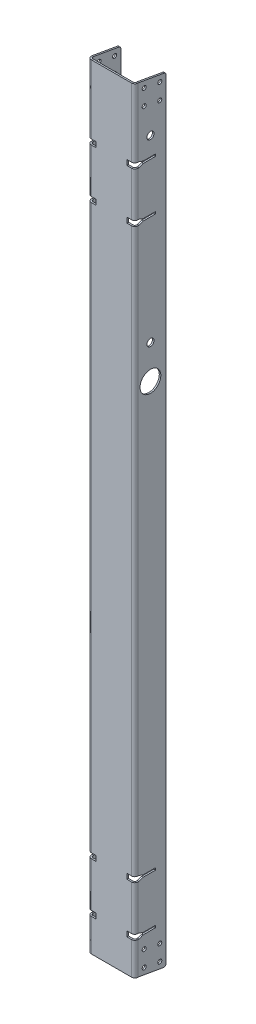
SolidWorks part; units mm, degrees
note: The reader was unsure of these and kept them because the rebuilt part matched: flange length of "Edge-Flange1", "Edge-Flange2".
ref_plane "Front Plane" through (0, 0, 0) normal (0, 0, 1) x (1, 0, 0)
ref_plane "Top Plane" through (0, 0, 0) normal (0, 1, 0) x (1, 0, 0)
ref_plane "Right Plane" through (0, 0, 0) normal (1, 0, 0) x (0, 0, -1)
sketch "Sketch1" plane through (0, 0, 0) normal (0, 0, 1) x (1, 0, 0)
  line L1 (28.575, 473.329) -> (-28.575, 473.329)
  line L2 (28.575, 473.329) -> (28.575, -473.329)
  line L3 (28.575, -473.329) -> (-28.575, -473.329)
  line L4 (-28.575, 473.329) -> (-28.575, -473.329)
  line L5 (28.575, 473.329) -> (-28.575, -473.329) construction
  line L6 (28.575, -473.329) -> (-28.575, 473.329) construction
  point P0 (0, 0)
  dimension "D1" = 57.15
  dimension "D2" = 946.658
base flange "Base-Flange1" sketch "Sketch1" thickness 1.8974 reverse thickness direction no parameters "D1"=2.032
edge flange "Edge-Flange1" sketch "Sketch8" flange angle 90 flange length 38.1 flange position material inside bend radius 2.032 thickness 1.8974 relief rectangular parameters "D6"=10
sketch "Sketch8" plane through (28.575, 0, -1.8974) normal (-1, 0, 0) x (0, 1, 0)
  line L0 (473.329, 2.8778) -> (467.4529, 36.2026)
  line L2 (-473.329, 0) -> (-473.329, 2.8778)
  line L3 (-479.2051, 36.2026) -> (467.4529, 36.2026)
  line L4 (473.329, 2.8778) -> (473.329, 0)
  line L5 (473.329, 0) -> (-473.329, 0) construction
  line L6 (473.329, 0) -> (-473.329, 0)
  line L7 (-473.329, 2.8778) -> (-479.2051, 36.2026)
  line L8 (473.329, -1.8974) -> (-473.329, -1.8974) construction
  dimension "D1" = 10
  dimension "D2" = 10
  dimension "D3" = 4.7752
  dimension "D4" = 4.7752
  dimension "D5" = 38.1
bend "EdgeBend1" bend radius 2.032 bend angle 90 parameters "D5"=1
edge flange "Edge-Flange2" sketch "Sketch11" flange angle 90 flange length 38.1 flange position material inside bend radius 2.032 thickness 1.8974 relief rectangular parameters "D6"=10
sketch "Sketch11" plane through (-28.575, 0, -1.8974) normal (1, 0, 0) x (0, -1, 0)
  line L0 (-473.329, 2.8778) -> (-467.4529, 36.2026)
  line L2 (-473.329, 0) -> (-473.329, 2.8778)
  line L3 (-467.4529, 36.2026) -> (479.2051, 36.2026)
  line L4 (473.329, 2.8778) -> (473.329, 0)
  line L5 (473.329, 0) -> (-473.329, 0) construction
  line L6 (473.329, 0) -> (-473.329, 0)
  line L7 (473.329, 2.8778) -> (479.2051, 36.2026)
  line L8 (473.329, -1.8974) -> (-473.329, -1.8974) construction
  dimension "D1" = 10
  dimension "D2" = 4.7752
  dimension "D3" = 38.1
  dimension "D4" = 10
  dimension "D5" = 4.7752
bend "EdgeBend2" bend radius 2.032 bend angle 90 parameters "D5"=2
fillet "Fillet1" radius 2.54 4 edges at (-27.6263, 467.4529, -38.1) (27.6263, 467.4529, -38.1) (-27.6263, -479.2051, -38.1) (27.6263, -479.2051, -38.1)
sketch "Sketch12" plane through (-28.575, 0, 0) normal (-1, 0, 0) x (0, 0, 1)
  line L0 (-38.1, -476.178) -> (-38.1, 465.3216) construction
  line L2 (-30.48, -450.78) -> (-11.43, -447.421) construction
  line L3 (-11.43, -447.421) -> (-11.43, -466.7649) construction
  line L4 (-11.43, -466.7649) -> (-30.48, -470.1239) construction
  line L5 (-30.48, -470.1239) -> (-30.48, -450.78) construction
  line L6 (-4.7752, -473.329) -> (-35.1189, -478.6794) construction
  circle A0 centre (-30.48, -470.1239) radius 2.4638
  circle A1 centre (-30.48, -450.78) radius 2.4638
  circle A2 centre (-11.43, -447.421) radius 2.4638
  circle A3 centre (-11.43, -466.7649) radius 2.4638
  dimension "D1" = 4.9276
  dimension "D2" = 7.62
  dimension "D3" = 19.05
  dimension "D4" = 7.62
  dimension "D5" = 19.05
extrude "Cut-Extrude1" cut sketch "Sketch12" against normal through all normal cut yes
sketch "Sketch13" plane through (-28.575, 0, 0) normal (-1, 0, 0) x (0, 0, 1)
  line L0 (-30.48, 461.059) -> (-11.43, 464.418) construction
  line L1 (-11.43, 464.418) -> (-11.43, 445.0742) construction
  line L2 (-11.43, 445.0742) -> (-30.48, 441.7151) construction
  line L3 (-30.48, 441.7151) -> (-30.48, 461.059) construction
  line L4 (-36.0011, 467.823) -> (-4.7752, 473.329) construction
  line L5 (-38.1, -476.178) -> (-38.1, 465.3216) construction
  circle A0 centre (-30.48, 461.059) radius 2.4638
  circle A1 centre (-11.43, 464.418) radius 2.4638
  circle A2 centre (-11.43, 445.0742) radius 2.4638
  circle A3 centre (-30.48, 441.7151) radius 2.4638
  dimension "D1" = 4.9276
  dimension "D2" = 7.62
  dimension "D3" = 19.05
  dimension "D4" = 7.62
  dimension "D5" = 19.05
extrude "Cut-Extrude2" cut sketch "Sketch13" against normal through all normal cut yes
sketch "Sketch14" plane through (-28.575, 0, 0) normal (-1, 0, 0) x (0, 0, 1)
  line L0 (3.175, 389.509) -> (3.175, 383.159)
  line L1 (-10.16, 387.604) -> (-25.4, 387.604)
  line L2 (-10.16, 385.064) -> (-25.4, 385.064)
  line L3 (-25.4, 387.604) -> (-25.4, 385.064)
  line L4 (3.175, 328.549) -> (3.175, 322.199)
  line L5 (-10.16, 326.644) -> (-25.4, 326.644)
  line L6 (-10.16, 324.104) -> (-25.4, 324.104)
  line L7 (-25.4, 326.644) -> (-25.4, 324.104)
  line L8 (-3.9294, -473.329) -> (-3.9294, 473.329) construction
  line L9 (0, 473.329) -> (0, -473.329) construction
  line L10 (-10.16, 387.604) -> (-5.08, 389.509)
  line L11 (-5.08, 389.509) -> (3.175, 389.509)
  line L12 (-10.16, 385.064) -> (-5.08, 383.159)
  line L13 (-5.08, 383.159) -> (3.175, 383.159)
  line L14 (0, 473.329) -> (-3.9294, 473.329) construction
  line L15 (-10.16, 326.644) -> (-5.08, 328.549)
  line L16 (-5.08, 328.549) -> (3.175, 328.549)
  line L17 (-10.16, 324.104) -> (-5.08, 322.199)
  line L18 (-5.08, 322.199) -> (3.175, 322.199)
  point P25 (0, 0)
  point P26 (0, 0)
  dimension "D1" = 2.54
  dimension "D2" = 63.5
  dimension "D3" = 28.575
  dimension "D4" = 25.4
  dimension "D5" = 85.725
  dimension "D6" = 6.35
  dimension "D7" = 5.08
  dimension "D8" = 10.16
extrude "Cut-Extrude3" cut sketch "Sketch14" against normal blind 9.525 normal cut yes
pattern_linear "LPattern1" count 2 spacing 755.65 along (0, -1, 0) of "Cut-Extrude3"
mirror "Mirror1" about plane through (0, 0, 0) normal (1, 0, 0) of "LPattern1", "Cut-Extrude3"
sketch "Sketch15" plane through (-28.575, 0, 0) normal (-1, 0, 0) x (0, 0, 1)
  line L0 (-36.0011, 467.823) -> (-4.7752, 473.329) construction
  line L1 (-38.1, -476.178) -> (-38.1, 465.3216) construction
  circle A0 centre (-19.05, 149.9615) radius 12.7
  dimension "D1" = 315.976
  dimension "D2" = 25.4
  dimension "D3" = 19.05
extrude "Cut-Extrude4" cut sketch "Sketch15" against normal through all normal cut yes
hole_wizard "11/32 (0.34375) Diameter Hole1" positions "Sketch16" profile "Sketch17" hole size "11/32" standard "ANSI Inch" end condition through all
sketch "Sketch16" plane through (-28.575, 0, 0) normal (-1, 0, 0) x (0, 0, 1)
  line L0 (-38.1, -476.178) -> (-38.1, 465.3216) construction
  line L1 (-36.0011, 467.823) -> (-4.7752, 473.329) construction
  point P0 (-19.05, 410.2012)
  point P2 (-19.05, 191.1262)
  dimension "D1" = 19.05
  dimension "D2" = 19.05
  dimension "D3" = 59.69
  dimension "D4" = 219.075
sketch "Sketch17" plane through (-28.575, 410.2012, -19.05) normal (0, 1, 0) x (0, 0, 1)
  line L0 (0, 0) -> (0, 57.15)
  line L1 (0, 57.15) -> (4.3656, 57.15)
  line L2 (4.3656, 57.15) -> (4.3656, 0)
  line L5 (4.3656, 0) -> (0, 0)
  line L11 (0, -6.35) -> (0, 107.95) construction
  dimension "Thru Hole Dia." = 8.7312
  dimension "Thru Hole Depth" = 57.15
sketch "Bend-Lines1" [suppressed] plane through (0, 0, 0) normal (0, 1, 0) x (1, 0, 0)
sketch "Bounding-Box1" [suppressed] plane through (0, 0, 0) normal (0, 1, 0) x (1, 0, 0)
sheet metal parameters "Sheet-Metal1" thickness 1.8974 parameters "D1"=2.032
flat pattern "Flat-Pattern1" [suppressed]
sketch "Bend-Lines2" plane through (0, 0, 0) normal (0, 1, 0) x (1, 0, 0)
sketch3d "Bounding-Box2" [suppressed]
  line L0 (-26.6776, 508, 0) -> (-26.6776, -508, 0) construction
  line L1 (26.6776, 508, 0) -> (26.6776, -508, 0) construction
  line L2 (-26.6776, 508, 0) -> (26.6776, 508, 0) construction
  line L3 (-26.6776, -508, 0) -> (26.6776, -508, 0) construction
sheet metal parameters "Sheet-Metal2" thickness 1.8974 parameters "D1"=2.032
flat pattern "Flat-Pattern1"
sketch "Bend-Lines2" plane through (0, 0, 0) normal (0, 0, 1) x (1, 0, 0)
  line L0 (25.0893, -508) -> (25.0893, 508) construction
  line L1 (25.0893, -508) -> (25.0893, 508) construction
sketch3d "Bounding-Box2" [suppressed]
  line L0 (61.6009, 508, 0) -> (61.6009, -508, 0) construction
  line L1 (-26.6776, 508, 0) -> (-26.6776, -508, 0) construction
  line L2 (61.6009, 508, 0) -> (-26.6776, 508, 0) construction
  line L3 (61.6009, -508, 0) -> (-26.6776, -508, 0) construction
bend of the flat pattern "Flatten-<EdgeBend1>1"
sheet metal parameters "Sheet-Metal3" thickness 1.8974 parameters "D1"=2.032
flat pattern "Flat-Pattern1"
sketch "Bend-Lines2" plane through (0, 0, 0) normal (0, 0, 1) x (1, 0, 0)
  line L0 (25.0893, -508) -> (25.0893, 508) construction
  line L1 (25.0893, -508) -> (25.0893, 508) construction
  line L2 (-25.0893, 508) -> (-25.0893, -508) construction
  line L3 (-25.0893, 508) -> (-25.0893, -508) construction
sketch3d "Bounding-Box2" [suppressed]
  line L0 (61.6008, -513.3886, 0) -> (61.6009, 508, 0) construction
  line L1 (-61.6009, -513.3886, 0) -> (-61.6008, 508, 0) construction
  line L2 (61.6008, -513.3886, 0) -> (-61.6009, -513.3886, 0) construction
  line L3 (61.6009, 508, 0) -> (-61.6008, 508, 0) construction
bend of the flat pattern "Flatten-<EdgeBend1>1"
bend of the flat pattern "Flatten-<EdgeBend2>1"
sheet metal parameters "Sheet-Metal4" thickness 1.8974 parameters "D1"=2.032
flat pattern "Flat-Pattern1"
sketch "Bend-Lines2" plane through (0, 0, 0) normal (0, 0, 1) x (1, 0, 0)
  line L0 (25.0893, -508) -> (25.0893, 508) construction
  line L1 (25.0893, -508) -> (25.0893, 508) construction
  line L2 (-25.0893, 508) -> (-25.0893, -508) construction
  line L3 (-25.0893, 508) -> (-25.0893, -508) construction
sketch3d "Bounding-Box2" [suppressed]
  line L0 (61.6008, -513.3886, 0) -> (61.6009, 508, 0) construction
  line L1 (-61.6009, -513.3886, 0) -> (-61.6008, 508, 0) construction
  line L2 (61.6008, -513.3886, 0) -> (-61.6009, -513.3886, 0) construction
  line L3 (61.6009, 508, 0) -> (-61.6008, 508, 0) construction
bend of the flat pattern "Flatten-<EdgeBend1>1"
bend of the flat pattern "Flatten-<EdgeBend2>1"
sheet metal parameters "Sheet-Metal5" thickness 1.8974 parameters "D1"=2.032
flat pattern "Flat-Pattern1"
sketch "Bend-Lines2" plane through (0, 0, 0) normal (0, 0, 1) x (1, 0, 0)
  line L0 (26.9866, -473.329) -> (26.9866, 473.329) construction
  line L1 (26.9866, -473.329) -> (26.9866, 473.329) construction
  line L2 (-26.9866, 473.329) -> (-26.9866, -473.329) construction
  line L3 (-26.9866, 473.329) -> (-26.9866, -473.329) construction
sketch3d "Bounding-Box2" [suppressed]
  line L0 (63.4982, -478.7176, 0) -> (63.4983, 473.329, 0) construction
  line L1 (-63.4983, -478.7176, 0) -> (-63.4982, 473.329, 0) construction
  line L2 (63.4982, -478.7176, 0) -> (-63.4983, -478.7176, 0) construction
  line L3 (63.4983, 473.329, 0) -> (-63.4982, 473.329, 0) construction
bend of the flat pattern "Flatten-<EdgeBend1>1"
bend of the flat pattern "Flatten-<EdgeBend2>1"
sheet metal parameters "Sheet-Metal6" thickness 1.8974 parameters "D1"=2.032
flat pattern "Flat-Pattern1"
sketch "Bend-Lines2" plane through (0, 0, 0) normal (0, 0, 1) x (1, 0, 0)
  line L0 (26.9866, -473.329) -> (26.9866, 473.329) construction
  line L1 (26.9866, -473.329) -> (26.9866, 473.329) construction
  line L2 (-26.9866, 419.989) -> (-26.9866, 361.569) construction
  line L3 (-26.9866, 419.989) -> (-26.9866, 361.569) construction
  line L4 (-26.9866, 359.029) -> (-26.9866, -473.329) construction
  line L5 (-26.9866, 473.329) -> (-26.9866, 422.529) construction
sketch3d "Bounding-Box2" [suppressed]
  line L0 (63.4982, -478.7176, 0) -> (63.4983, 473.329, 0) construction
  line L1 (-63.4983, -478.7176, 0) -> (-63.4982, 473.329, 0) construction
  line L2 (63.4982, -478.7176, 0) -> (-63.4983, -478.7176, 0) construction
  line L3 (63.4983, 473.329, 0) -> (-63.4982, 473.329, 0) construction
bend of the flat pattern "Flatten-<EdgeBend1>1"
bend of the flat pattern "Flatten-<EdgeBend2>1"
sheet metal parameters "Sheet-Metal7" thickness 1.8974 parameters "D1"=2.032
flat pattern "Flat-Pattern1"
sketch "Bend-Lines2" plane through (0, 0, 0) normal (0, 0, 1) x (1, 0, 0)
  line L0 (26.9866, -473.329) -> (26.9866, 473.329) construction
  line L1 (26.9866, -473.329) -> (26.9866, 473.329) construction
  line L2 (-26.9866, -354.711) -> (-26.9866, -413.131) construction
  line L3 (-26.9866, -354.711) -> (-26.9866, -413.131) construction
  line L4 (-26.9866, -415.671) -> (-26.9866, -473.329) construction
  line L5 (-26.9866, 473.329) -> (-26.9866, 422.529) construction
  line L6 (-26.9866, 419.989) -> (-26.9866, 361.569) construction
  line L7 (-26.9866, 359.029) -> (-26.9866, -352.171) construction
sketch3d "Bounding-Box2" [suppressed]
  line L0 (63.4982, -478.7176, 0) -> (63.4983, 473.329, 0) construction
  line L1 (-63.4983, -478.7176, 0) -> (-63.4982, 473.329, 0) construction
  line L2 (63.4982, -478.7176, 0) -> (-63.4983, -478.7176, 0) construction
  line L3 (63.4983, 473.329, 0) -> (-63.4982, 473.329, 0) construction
bend of the flat pattern "Flatten-<EdgeBend1>1"
bend of the flat pattern "Flatten-<EdgeBend2>1"
sheet metal parameters "Sheet-Metal8" thickness 1.8974 parameters "D1"=2.032
flat pattern "Flat-Pattern1"
sketch "Bend-Lines2" plane through (0, 0, 0) normal (0, 0, 1) x (1, 0, 0)
  line L0 (26.9866, 361.569) -> (26.9866, 419.989) construction
  line L1 (26.9866, 361.569) -> (26.9866, 419.989) construction
  line L2 (-26.9866, 473.329) -> (-26.9866, 422.529) construction
  line L3 (-26.9866, 473.329) -> (-26.9866, 422.529) construction
  line L4 (-26.9866, 419.989) -> (-26.9866, 361.569) construction
  line L5 (-26.9866, 359.029) -> (-26.9866, -352.171) construction
  line L6 (-26.9866, -354.711) -> (-26.9866, -413.131) construction
  line L7 (-26.9866, -415.671) -> (-26.9866, -473.329) construction
  line L8 (26.9866, 422.529) -> (26.9866, 473.329) construction
  line L9 (26.9866, -473.329) -> (26.9866, -415.671) construction
  line L10 (26.9866, -413.131) -> (26.9866, -354.711) construction
  line L11 (26.9866, -352.171) -> (26.9866, 359.029) construction
sketch3d "Bounding-Box2" [suppressed]
  line L0 (63.4982, -478.7176, 0) -> (63.4983, 473.329, 0) construction
  line L1 (-63.4983, -478.7176, 0) -> (-63.4982, 473.329, 0) construction
  line L2 (63.4982, -478.7176, 0) -> (-63.4983, -478.7176, 0) construction
  line L3 (63.4983, 473.329, 0) -> (-63.4982, 473.329, 0) construction
bend of the flat pattern "Flatten-<EdgeBend1>1"
bend of the flat pattern "Flatten-<EdgeBend2>1"
sheet metal parameters "Sheet-Metal9" thickness 1.8974 parameters "D1"=2.032
flat pattern "Flat-Pattern1"
sketch "Bend-Lines2" plane through (0, 0, 0) normal (0, 0, 1) x (1, 0, 0)
  line L0 (26.9866, 361.569) -> (26.9866, 419.989) construction
  line L1 (26.9866, 361.569) -> (26.9866, 419.989) construction
  line L2 (-26.9866, 473.329) -> (-26.9866, 422.529) construction
  line L3 (-26.9866, 473.329) -> (-26.9866, 422.529) construction
  line L4 (-26.9866, 419.989) -> (-26.9866, 361.569) construction
  line L5 (-26.9866, 359.029) -> (-26.9866, -352.171) construction
  line L6 (-26.9866, -354.711) -> (-26.9866, -413.131) construction
  line L7 (-26.9866, -415.671) -> (-26.9866, -473.329) construction
  line L8 (26.9866, 422.529) -> (26.9866, 473.329) construction
  line L9 (26.9866, -473.329) -> (26.9866, -415.671) construction
  line L10 (26.9866, -413.131) -> (26.9866, -354.711) construction
  line L11 (26.9866, -352.171) -> (26.9866, 359.029) construction
sketch3d "Bounding-Box2" [suppressed]
  line L0 (63.4982, -478.7176, 0) -> (63.4983, 473.329, 0) construction
  line L1 (-63.4983, -478.7176, 0) -> (-63.4982, 473.329, 0) construction
  line L2 (63.4982, -478.7176, 0) -> (-63.4983, -478.7176, 0) construction
  line L3 (63.4983, 473.329, 0) -> (-63.4982, 473.329, 0) construction
bend of the flat pattern "Flatten-<EdgeBend1>1"
bend of the flat pattern "Flatten-<EdgeBend2>1"
sheet metal parameters "Sheet-Metal10" thickness 1.8974 parameters "D1"=2.032
flat pattern "Flat-Pattern1"
sketch "Bend-Lines2" plane through (0, 0, 0) normal (0, 0, 1) x (1, 0, 0)
  line L0 (26.9866, -366.141) -> (26.9866, 322.199) construction
  line L1 (26.9866, -366.141) -> (26.9866, 322.199) construction
  line L2 (-26.9866, 473.329) -> (-26.9866, 389.509) construction
  line L3 (-26.9866, 473.329) -> (-26.9866, 389.509) construction
  line L4 (-26.9866, 383.159) -> (-26.9866, 328.549) construction
  line L5 (-26.9866, 322.199) -> (-26.9866, -366.141) construction
  line L6 (-26.9866, -372.491) -> (-26.9866, -427.101) construction
  line L7 (-26.9866, -433.451) -> (-26.9866, -473.329) construction
  line L8 (26.9866, 328.549) -> (26.9866, 383.159) construction
  line L9 (26.9866, 389.509) -> (26.9866, 473.329) construction
  line L10 (26.9866, -473.329) -> (26.9866, -433.451) construction
  line L11 (26.9866, -427.101) -> (26.9866, -372.491) construction
sketch3d "Bounding-Box2" [suppressed]
  line L0 (63.4982, -478.7176, 0) -> (63.4983, 473.329, 0) construction
  line L1 (-63.4983, -478.7176, 0) -> (-63.4982, 473.329, 0) construction
  line L2 (63.4982, -478.7176, 0) -> (-63.4983, -478.7176, 0) construction
  line L3 (63.4983, 473.329, 0) -> (-63.4982, 473.329, 0) construction
bend of the flat pattern "Flatten-<EdgeBend1>1"
bend of the flat pattern "Flatten-<EdgeBend2>1"
